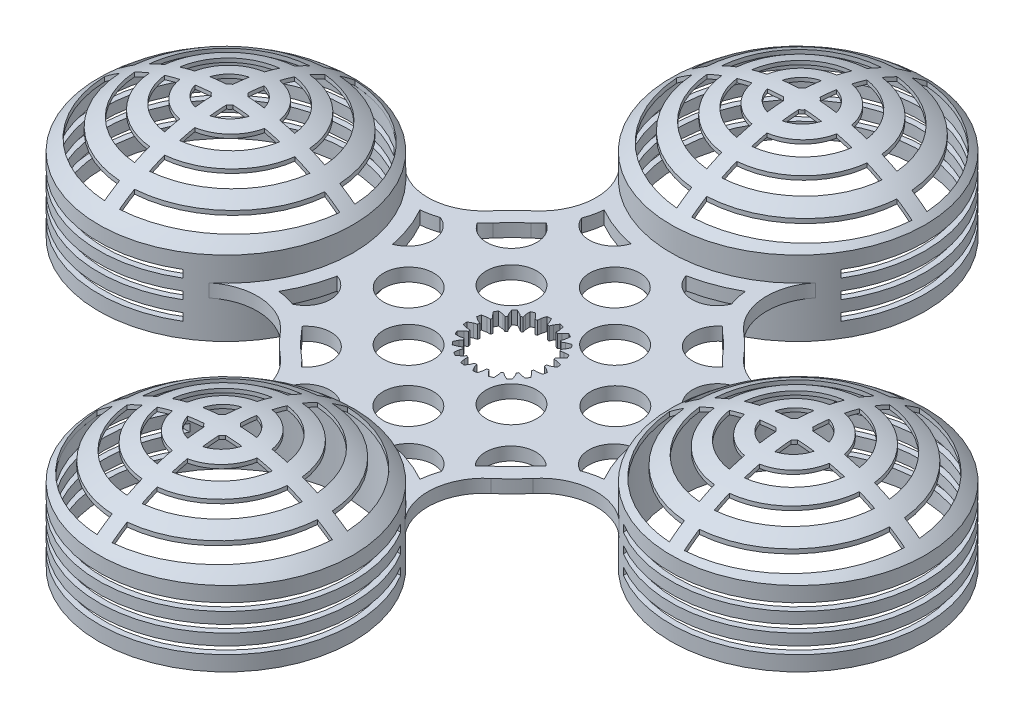
SolidWorks part; units mm, degrees
note: The reader was unsure of these and kept them because the rebuilt part matched: shared geometry of "Çizim1<3>".
ref_plane "Ön Düzlem" through (0, 0, 0) normal (0, 0, 1) x (1, 0, 0)
ref_plane "Üst Düzlem" through (0, 0, 0) normal (0, 1, 0) x (1, 0, 0)
ref_plane "Sağ Düzlem" through (0, 0, 0) normal (1, 0, 0) x (0, 0, -1)
sketch "Çizim1" plane through (0, 0, 0) normal (0, 1, 0) x (1, 0, 0)
  circle A0 centre (0, 0) radius 43.9658
  circle A1 centre (76.4658, 0) radius 32.5
  circle A2 centre (0, -76.4658) radius 32.5
  circle A3 centre (-76.4658, 0) radius 32.5
  circle A4 centre (0, 76.4658) radius 32.5
  point P14 (0, 0)
  dimension "D2" = 65
  dimension "D3" = 87.9316
  dimension "D1" = 4
extrude "Yükseklik-Ekstrüzyon1" add sketch "Çizim1" along normal blind 3.5 contours A0
extrude "Ekstrüzyon-İnce1" add sketch "Çizim1<3>" along normal mid plane 20 thin contours A3 | A2 | A1 | A4
sketch "Çizim1<3>" plane through (0, 0, 0) normal (0, 1, 0) x (1, 0, 0) same geometry as "Çizim1"
sketch "Çizim2" plane through (0, 3.5, 0) normal (0, 1, 0) x (1, 0, 0)
  line L0 (-2.9974, -9.6557) -> (-2.7583, -10.9582)
  line L1 (-1.7004, -11.1713) -> (-0.9756, -10.063)
  line L2 (-0.9756, -10.063) -> (-0.6518, -9.2771)
  line L3 (-0.1241, -9.2992) -> (0.1331, -10.1093)
  line L4 (0.1331, -10.1093) -> (0.7629, -11.2742)
  line L5 (1.835, -11.15) -> (2.1818, -9.872)
  line L6 (2.1818, -9.872) -> (2.2469, -9.0245)
  line L7 (2.7556, -8.8824) -> (3.2505, -9.5734)
  line L8 (3.2505, -9.5734) -> (4.2095, -10.4867)
  line L9 (5.1907, -10.0373) -> (5.1257, -8.7146)
  line L10 (5.1257, -8.7146) -> (4.9257, -7.8885)
  line L11 (5.3655, -7.5961) -> (6.0498, -8.1004)
  line L12 (6.0498, -8.1004) -> (7.244, -8.6726)
  line L13 (8.0383, -7.942) -> (7.5677, -6.7042)
  line L14 (7.5677, -6.7042) -> (7.1223, -5.9803)
  line L15 (7.4503, -5.5663) -> (8.2568, -5.8345)
  line L16 (8.2568, -5.8345) -> (9.5695, -6.0096)
  line L17 (10.0991, -5.0693) -> (9.269, -4.0375)
  line L18 (9.269, -4.0375) -> (8.6217, -3.4867)
  line L19 (8.8057, -2.9916) -> (9.6557, -2.9974)
  line L20 (9.6557, -2.9974) -> (10.9582, -2.7583)
  line L21 (11.1713, -1.7004) -> (10.063, -0.9756)
  line L22 (10.063, -0.9756) -> (9.2771, -0.6518)
  line L23 (9.2992, -0.1241) -> (10.1093, 0.1331)
  line L24 (10.1093, 0.1331) -> (11.2742, 0.7629)
  line L25 (11.15, 1.835) -> (9.872, 2.1818)
  line L26 (9.872, 2.1818) -> (9.0245, 2.2469)
  line L27 (8.8824, 2.7556) -> (9.5734, 3.2505)
  line L28 (9.5734, 3.2505) -> (10.4867, 4.2095)
  line L29 (10.0373, 5.1907) -> (8.7146, 5.1257)
  line L30 (8.7146, 5.1257) -> (7.8885, 4.9257)
  line L31 (7.5961, 5.3655) -> (8.1004, 6.0498)
  line L32 (8.1004, 6.0498) -> (8.6726, 7.244)
  line L33 (7.942, 8.0383) -> (6.7042, 7.5677)
  line L34 (6.7042, 7.5677) -> (5.9803, 7.1223)
  line L35 (5.5663, 7.4503) -> (5.8345, 8.2568)
  line L36 (5.8345, 8.2568) -> (6.0096, 9.5695)
  line L37 (5.0693, 10.0991) -> (4.0375, 9.269)
  line L38 (4.0375, 9.269) -> (3.4867, 8.6217)
  line L39 (2.9916, 8.8057) -> (2.9974, 9.6557)
  line L40 (2.9974, 9.6557) -> (2.7583, 10.9582)
  line L41 (1.7004, 11.1713) -> (0.9756, 10.063)
  line L42 (0.9756, 10.063) -> (0.6518, 9.2771)
  line L43 (0.1241, 9.2992) -> (-0.1331, 10.1093)
  line L44 (-0.1331, 10.1093) -> (-0.7629, 11.2742)
  line L45 (-1.835, 11.15) -> (-2.1818, 9.872)
  line L46 (-2.1818, 9.872) -> (-2.2469, 9.0245)
  line L47 (-2.7556, 8.8824) -> (-3.2505, 9.5734)
  line L48 (-3.2505, 9.5734) -> (-4.2095, 10.4867)
  line L49 (-5.1907, 10.0373) -> (-5.1257, 8.7146)
  line L50 (-5.1257, 8.7146) -> (-4.9257, 7.8885)
  line L51 (-5.3655, 7.5961) -> (-6.0498, 8.1004)
  line L52 (-6.0498, 8.1004) -> (-7.244, 8.6726)
  line L53 (-8.0383, 7.942) -> (-7.5677, 6.7042)
  line L54 (-7.5677, 6.7042) -> (-7.1223, 5.9803)
  line L55 (-7.4503, 5.5663) -> (-8.2568, 5.8345)
  line L56 (-8.2568, 5.8345) -> (-9.5695, 6.0096)
  line L57 (-10.0991, 5.0693) -> (-9.269, 4.0375)
  line L58 (-9.269, 4.0375) -> (-8.6217, 3.4867)
  line L59 (-8.8057, 2.9916) -> (-9.6557, 2.9974)
  line L60 (-9.6557, 2.9974) -> (-10.9582, 2.7583)
  line L61 (-11.1713, 1.7004) -> (-10.063, 0.9756)
  line L62 (-10.063, 0.9756) -> (-9.2771, 0.6518)
  line L63 (-9.2992, 0.1241) -> (-10.1093, -0.1331)
  line L64 (-10.1093, -0.1331) -> (-11.2742, -0.7629)
  line L65 (-11.15, -1.835) -> (-9.872, -2.1818)
  line L66 (-9.872, -2.1818) -> (-9.0245, -2.2469)
  line L67 (-8.8824, -2.7556) -> (-9.5734, -3.2505)
  line L68 (-9.5734, -3.2505) -> (-10.4867, -4.2095)
  line L69 (-10.0373, -5.1907) -> (-8.7146, -5.1257)
  line L70 (-8.7146, -5.1257) -> (-7.8885, -4.9257)
  line L71 (-7.5961, -5.3655) -> (-8.1004, -6.0498)
  line L72 (-8.1004, -6.0498) -> (-8.6726, -7.244)
  line L73 (-7.942, -8.0383) -> (-6.7042, -7.5677)
  line L74 (-6.7042, -7.5677) -> (-5.9803, -7.1223)
  line L75 (-5.5663, -7.4503) -> (-5.8345, -8.2568)
  line L76 (-5.8345, -8.2568) -> (-6.0096, -9.5695)
  line L77 (-5.0693, -10.0991) -> (-4.0375, -9.269)
  line L78 (-4.0375, -9.269) -> (-3.4867, -8.6217)
  line L79 (-2.9916, -8.8057) -> (-2.9974, -9.6557)
  line L160 (-2.6972, -9.6294) -> (-2.4984, -10.7125)
  line L161 (-1.8449, -10.8442) -> (-1.2422, -9.9226)
  line L162 (-1.2422, -9.9226) -> (-0.8457, -8.9602)
  line L163 (0.0956, -8.9995) -> (0.4104, -9.9916)
  line L164 (0.4104, -9.9916) -> (0.9342, -10.9603)
  line L165 (1.5965, -10.8835) -> (1.8849, -9.8208)
  line L166 (1.8849, -9.8208) -> (1.9646, -8.783)
  line L167 (2.8719, -8.5295) -> (3.4779, -9.3757)
  line L168 (3.4779, -9.3757) -> (4.2754, -10.1351)
  line L169 (4.8815, -9.8575) -> (4.8274, -8.7576)
  line L170 (4.8274, -8.7576) -> (4.5825, -7.746)
  line L171 (5.3671, -7.2246) -> (6.2049, -7.8421)
  line L172 (6.2049, -7.8421) -> (7.1981, -8.3179)
  line L173 (7.6887, -7.8666) -> (7.2974, -6.8373)
  line L174 (7.2974, -6.8373) -> (6.7519, -5.9508)
  line L175 (7.3369, -5.2125) -> (8.3246, -5.5409)
  line L176 (8.3246, -5.5409) -> (9.4162, -5.6865)
  line L177 (9.7433, -5.1056) -> (9.0531, -4.2476)
  line L178 (9.0531, -4.2476) -> (8.2603, -3.5731)
  line L179 (8.5886, -2.6901) -> (9.6294, -2.6972)
  line L180 (9.6294, -2.6972) -> (10.7125, -2.4984)
  line L181 (10.8442, -1.8449) -> (9.9226, -1.2422)
  line L182 (9.9226, -1.2422) -> (8.9602, -0.8457)
  line L183 (8.9995, 0.0956) -> (9.9916, 0.4104)
  line L184 (9.9916, 0.4104) -> (10.9603, 0.9342)
  line L185 (10.8835, 1.5965) -> (9.8208, 1.8849)
  line L186 (9.8208, 1.8849) -> (8.783, 1.9646)
  line L187 (8.5295, 2.8719) -> (9.3757, 3.4779)
  line L188 (9.3757, 3.4779) -> (10.1351, 4.2754)
  line L189 (9.8575, 4.8815) -> (8.7576, 4.8274)
  line L190 (8.7576, 4.8274) -> (7.746, 4.5825)
  line L191 (7.2246, 5.3671) -> (7.8421, 6.2049)
  line L192 (7.8421, 6.2049) -> (8.3179, 7.1981)
  line L193 (7.8666, 7.6887) -> (6.8373, 7.2974)
  line L194 (6.8373, 7.2974) -> (5.9508, 6.7519)
  line L195 (5.2125, 7.3369) -> (5.5409, 8.3246)
  line L196 (5.5409, 8.3246) -> (5.6865, 9.4162)
  line L197 (5.1056, 9.7433) -> (4.2476, 9.0531)
  line L198 (4.2476, 9.0531) -> (3.5731, 8.2603)
  line L199 (2.6901, 8.5886) -> (2.6972, 9.6294)
  line L200 (2.6972, 9.6294) -> (2.4984, 10.7125)
  line L201 (1.8449, 10.8442) -> (1.2422, 9.9226)
  line L202 (1.2422, 9.9226) -> (0.8457, 8.9602)
  line L203 (-0.0956, 8.9995) -> (-0.4104, 9.9916)
  line L204 (-0.4104, 9.9916) -> (-0.9342, 10.9603)
  line L205 (-1.5965, 10.8835) -> (-1.8849, 9.8208)
  line L206 (-1.8849, 9.8208) -> (-1.9646, 8.783)
  line L207 (-2.8719, 8.5295) -> (-3.4779, 9.3757)
  line L208 (-3.4779, 9.3757) -> (-4.2754, 10.1351)
  line L209 (-4.8815, 9.8575) -> (-4.8274, 8.7576)
  line L210 (-4.8274, 8.7576) -> (-4.5825, 7.746)
  line L211 (-5.3671, 7.2246) -> (-6.2049, 7.8421)
  line L212 (-6.2049, 7.8421) -> (-7.1981, 8.3179)
  line L213 (-7.6887, 7.8666) -> (-7.2974, 6.8373)
  line L214 (-7.2974, 6.8373) -> (-6.7519, 5.9508)
  line L215 (-7.3369, 5.2125) -> (-8.3246, 5.5409)
  line L216 (-8.3246, 5.5409) -> (-9.4162, 5.6865)
  line L217 (-9.7433, 5.1056) -> (-9.0531, 4.2476)
  line L218 (-9.0531, 4.2476) -> (-8.2603, 3.5731)
  line L219 (-8.5886, 2.6901) -> (-9.6294, 2.6972)
  line L220 (-9.6294, 2.6972) -> (-10.7125, 2.4984)
  line L221 (-10.8442, 1.8449) -> (-9.9226, 1.2422)
  line L222 (-9.9226, 1.2422) -> (-8.9602, 0.8457)
  line L223 (-8.9995, -0.0956) -> (-9.9916, -0.4104)
  line L224 (-9.9916, -0.4104) -> (-10.9603, -0.9342)
  line L225 (-10.8835, -1.5965) -> (-9.8208, -1.8849)
  line L226 (-9.8208, -1.8849) -> (-8.783, -1.9646)
  line L227 (-8.5295, -2.8719) -> (-9.3757, -3.4779)
  line L228 (-9.3757, -3.4779) -> (-10.1351, -4.2754)
  line L229 (-9.8575, -4.8815) -> (-8.7576, -4.8274)
  line L230 (-8.7576, -4.8274) -> (-7.746, -4.5825)
  line L231 (-7.2246, -5.3671) -> (-7.8421, -6.2049)
  line L232 (-7.8421, -6.2049) -> (-8.3179, -7.1981)
  line L233 (-7.8666, -7.6887) -> (-6.8373, -7.2974)
  line L234 (-6.8373, -7.2974) -> (-5.9508, -6.7519)
  line L235 (-5.2125, -7.3369) -> (-5.5409, -8.3246)
  line L236 (-5.5409, -8.3246) -> (-5.6865, -9.4162)
  line L237 (-5.1056, -9.7433) -> (-4.2476, -9.0531)
  line L238 (-4.2476, -9.0531) -> (-3.5731, -8.2603)
  line L239 (-2.6901, -8.5886) -> (-2.6972, -9.6294)
  arc A0 (-2.7583, -10.9582) -> (-1.7004, -11.1713) centre (0, 0) ccw
  arc A1 (-0.6518, -9.2771) -> (-0.1241, -9.2992) centre (0, 0) ccw
  arc A2 (0.7629, -11.2742) -> (1.835, -11.15) centre (0, 0) ccw
  arc A3 (2.2469, -9.0245) -> (2.7556, -8.8824) centre (0, 0) ccw
  arc A4 (4.2095, -10.4867) -> (5.1907, -10.0373) centre (0, 0) ccw
  arc A5 (4.9257, -7.8885) -> (5.3655, -7.5961) centre (0, 0) ccw
  arc A6 (7.244, -8.6726) -> (8.0383, -7.942) centre (0, 0) ccw
  arc A7 (7.1223, -5.9803) -> (7.4503, -5.5663) centre (0, 0) ccw
  arc A8 (9.5695, -6.0096) -> (10.0991, -5.0693) centre (0, 0) ccw
  arc A9 (8.6217, -3.4867) -> (8.8057, -2.9916) centre (0, 0) ccw
  arc A10 (10.9582, -2.7583) -> (11.1713, -1.7004) centre (0, 0) ccw
  arc A11 (9.2771, -0.6518) -> (9.2992, -0.1241) centre (0, 0) ccw
  arc A12 (11.2742, 0.7629) -> (11.15, 1.835) centre (0, 0) ccw
  arc A13 (9.0245, 2.2469) -> (8.8824, 2.7556) centre (0, 0) ccw
  arc A14 (10.4867, 4.2095) -> (10.0373, 5.1907) centre (0, 0) ccw
  arc A15 (7.8885, 4.9257) -> (7.5961, 5.3655) centre (0, 0) ccw
  arc A16 (8.6726, 7.244) -> (7.942, 8.0383) centre (0, 0) ccw
  arc A17 (5.9803, 7.1223) -> (5.5663, 7.4503) centre (0, 0) ccw
  arc A18 (6.0096, 9.5695) -> (5.0693, 10.0991) centre (0, 0) ccw
  arc A19 (3.4867, 8.6217) -> (2.9916, 8.8057) centre (0, 0) ccw
  arc A20 (2.7583, 10.9582) -> (1.7004, 11.1713) centre (0, 0) ccw
  arc A21 (0.6518, 9.2771) -> (0.1241, 9.2992) centre (0, 0) ccw
  arc A22 (-0.7629, 11.2742) -> (-1.835, 11.15) centre (0, 0) ccw
  arc A23 (-2.2469, 9.0245) -> (-2.7556, 8.8824) centre (0, 0) ccw
  arc A24 (-4.2095, 10.4867) -> (-5.1907, 10.0373) centre (0, 0) ccw
  arc A25 (-4.9257, 7.8885) -> (-5.3655, 7.5961) centre (0, 0) ccw
  arc A26 (-7.244, 8.6726) -> (-8.0383, 7.942) centre (0, 0) ccw
  arc A27 (-7.1223, 5.9803) -> (-7.4503, 5.5663) centre (0, 0) ccw
  arc A28 (-9.5695, 6.0096) -> (-10.0991, 5.0693) centre (0, 0) ccw
  arc A29 (-8.6217, 3.4867) -> (-8.8057, 2.9916) centre (0, 0) ccw
  arc A30 (-10.9582, 2.7583) -> (-11.1713, 1.7004) centre (0, 0) ccw
  arc A31 (-9.2771, 0.6518) -> (-9.2992, 0.1241) centre (0, 0) ccw
  arc A32 (-11.2742, -0.7629) -> (-11.15, -1.835) centre (0, 0) ccw
  arc A33 (-9.0245, -2.2469) -> (-8.8824, -2.7556) centre (0, 0) ccw
  arc A34 (-10.4867, -4.2095) -> (-10.0373, -5.1907) centre (0, 0) ccw
  arc A35 (-7.8885, -4.9257) -> (-7.5961, -5.3655) centre (0, 0) ccw
  arc A36 (-8.6726, -7.244) -> (-7.942, -8.0383) centre (0, 0) ccw
  arc A37 (-5.9803, -7.1223) -> (-5.5663, -7.4503) centre (0, 0) ccw
  arc A38 (-6.0096, -9.5695) -> (-5.0693, -10.0991) centre (0, 0) ccw
  arc A39 (-3.4867, -8.6217) -> (-2.9916, -8.8057) centre (0, 0) ccw
  arc A80 (-2.4984, -10.7125) -> (-1.8449, -10.8442) centre (0, 0) ccw
  arc A81 (-0.8457, -8.9602) -> (0.0956, -8.9995) centre (0, 0) ccw
  arc A82 (0.9342, -10.9603) -> (1.5965, -10.8835) centre (0, 0) ccw
  arc A83 (1.9646, -8.783) -> (2.8719, -8.5295) centre (0, 0) ccw
  arc A84 (4.2754, -10.1351) -> (4.8815, -9.8575) centre (0, 0) ccw
  arc A85 (4.5825, -7.746) -> (5.3671, -7.2246) centre (0, 0) ccw
  arc A86 (7.1981, -8.3179) -> (7.6887, -7.8666) centre (0, 0) ccw
  arc A87 (6.7519, -5.9508) -> (7.3369, -5.2125) centre (0, 0) ccw
  arc A88 (9.4162, -5.6865) -> (9.7433, -5.1056) centre (0, 0) ccw
  arc A89 (8.2603, -3.5731) -> (8.5886, -2.6901) centre (0, 0) ccw
  arc A90 (10.7125, -2.4984) -> (10.8442, -1.8449) centre (0, 0) ccw
  arc A91 (8.9602, -0.8457) -> (8.9995, 0.0956) centre (0, 0) ccw
  arc A92 (10.9603, 0.9342) -> (10.8835, 1.5965) centre (0, 0) ccw
  arc A93 (8.783, 1.9646) -> (8.5295, 2.8719) centre (0, 0) ccw
  arc A94 (10.1351, 4.2754) -> (9.8575, 4.8815) centre (0, 0) ccw
  arc A95 (7.746, 4.5825) -> (7.2246, 5.3671) centre (0, 0) ccw
  arc A96 (8.3179, 7.1981) -> (7.8666, 7.6887) centre (0, 0) ccw
  arc A97 (5.9508, 6.7519) -> (5.2125, 7.3369) centre (0, 0) ccw
  arc A98 (5.6865, 9.4162) -> (5.1056, 9.7433) centre (0, 0) ccw
  arc A99 (3.5731, 8.2603) -> (2.6901, 8.5886) centre (0, 0) ccw
  arc A100 (2.4984, 10.7125) -> (1.8449, 10.8442) centre (0, 0) ccw
  arc A101 (0.8457, 8.9602) -> (-0.0956, 8.9995) centre (0, 0) ccw
  arc A102 (-0.9342, 10.9603) -> (-1.5965, 10.8835) centre (0, 0) ccw
  arc A103 (-1.9646, 8.783) -> (-2.8719, 8.5295) centre (0, 0) ccw
  arc A104 (-4.2754, 10.1351) -> (-4.8815, 9.8575) centre (0, 0) ccw
  arc A105 (-4.5825, 7.746) -> (-5.3671, 7.2246) centre (0, 0) ccw
  arc A106 (-7.1981, 8.3179) -> (-7.6887, 7.8666) centre (0, 0) ccw
  arc A107 (-6.7519, 5.9508) -> (-7.3369, 5.2125) centre (0, 0) ccw
  arc A108 (-9.4162, 5.6865) -> (-9.7433, 5.1056) centre (0, 0) ccw
  arc A109 (-8.2603, 3.5731) -> (-8.5886, 2.6901) centre (0, 0) ccw
  arc A110 (-10.7125, 2.4984) -> (-10.8442, 1.8449) centre (0, 0) ccw
  arc A111 (-8.9602, 0.8457) -> (-8.9995, -0.0956) centre (0, 0) ccw
  arc A112 (-10.9603, -0.9342) -> (-10.8835, -1.5965) centre (0, 0) ccw
  arc A113 (-8.783, -1.9646) -> (-8.5295, -2.8719) centre (0, 0) ccw
  arc A114 (-10.1351, -4.2754) -> (-9.8575, -4.8815) centre (0, 0) ccw
  arc A115 (-7.746, -4.5825) -> (-7.2246, -5.3671) centre (0, 0) ccw
  arc A116 (-8.3179, -7.1981) -> (-7.8666, -7.6887) centre (0, 0) ccw
  arc A117 (-5.9508, -6.7519) -> (-5.2125, -7.3369) centre (0, 0) ccw
  arc A118 (-5.6865, -9.4162) -> (-5.1056, -9.7433) centre (0, 0) ccw
  arc A119 (-3.5731, -8.2603) -> (-2.6901, -8.5886) centre (0, 0) ccw
  dimension "D2" = 0.3
extrude "Kes-Ekstrüzyon1" cut sketch "Çizim2" against normal through all contours L238 A119 L239 L160 A80 L161 L162 A81 L163 L164 A82 L165 L166 A83 L167 L168 A84 L169 L170 A85 L171 L172 A86 L173 L174 A87 L175 L176 A88 L177 L178 A89 L179 L180 A90 L181 L182 A91 L183 L184 A92 L185 L186 A93 L187 L188 A94 L189 L190 A95 L191 | L78 A39 L79 L0 A0 L1 L2 A1 L3 L4 A2 L5 L6 A3 L7 L8 A4 L9 L10 A5 L11 L12 A6 L13 L14 A7 L15 L16 A8 L17 L18 A9 L19 L20 A10 L21 L22 A11 L23 L24 A12 L25 L26 A13 L27 L28 A14 L29 L30 A15 L31
sketch "Çizim3" plane through (0, 3.5, 0) normal (0, 1, 0) x (1, 0, 0)
  line L0 (107.611, -9.2857) -> (45.3206, 9.2857)
  circle A1 centre (76.4658, 0) radius 32.5
  circle A3 centre (76.4658, 0) radius 32.5 construction
  point P11 (76.4658, 0)
ref_plane "Düzlem1" through (6.2421, 0, -20.9367) normal (0.2857, 0, -0.9583) x (-0.9583, 0, -0.2857)
sketch "Çizim4" plane through (6.2421, 0, -20.9367) normal (0.2857, 0, -0.9583) x (-0.9583, 0, -0.2857)
  line L0 (-39.2783, 10) -> (-107.2783, 10) construction
  line L1 (-40.7783, 10) -> (-105.7783, 10) construction
  line L3 (-73.2783, 30.9693) -> (-73.2783, 0)
  line L4 (-39.2783, -10) -> (-39.2783, 10) construction
  line L5 (-40.7783, 10) -> (-105.7783, 10)
  line L6 (-105.7783, 10) -> (-107.2783, 10)
  line L7 (-40.7783, 10) -> (-39.2783, 10)
  arc A3 (-107.2783, 10) -> (-39.2783, 10) centre (-73.2783, -28.9287) cw
  arc A4 (-105.7783, 10) -> (-40.7783, 10) centre (-73.2783, -28.9287) cw
  arc A5 (-106.6402, 9.2639) -> (-39.9191, 9.2663) centre (-73.2783, -28.9287) cw construction
  arc A6 (-107.2811, 9.9976) -> (-39.2783, 10) centre (-73.2783, -28.9287) cw construction
revolve "Döndür5" add sketch "Çizim4" angle 360 about L3
pattern_circular "Dairesel Kaplama1" count 4 over 360 about axis through (0, 0, 0) along (0, 1, 0) of "Döndür5"
fillet "Radyus1" radius 15 8 edges at (-7.5451, 1.75, 43.3135) (7.5451, 1.75, 43.3135) (-43.3135, 1.75, -7.5451) (-43.3135, 1.75, 7.5451) (43.3135, 1.75, 7.5451) (43.3135, 1.75, -7.5451) (7.5451, 1.75, -43.3135) (-7.5451, 1.75, -43.3135)
sketch "Çizim6" plane through (0, 3.5, 0) normal (0, 1, 0) x (1, 0, 0)
  line L1 (-52.2515, 78.4593) -> (48.6953, 78.4593)
  line L2 (-52.2515, 78.4593) -> (-52.2515, 74.4593)
  line L3 (-52.2515, 74.4593) -> (48.6953, 74.4593)
  line L4 (48.6953, 78.4593) -> (48.6953, 74.4593)
  line L5 (-1.0076, 123.3421) -> (2.9924, 123.3421)
  line L6 (-1.0076, 123.3421) -> (-1.0076, 29.9642)
  line L7 (-1.0076, 29.9642) -> (2.9924, 29.9642)
  line L8 (2.9924, 123.3421) -> (2.9924, 29.9642)
  circle A0 centre (0.9924, 76.4593) radius 31.5
  circle A1 centre (0.9924, 76.4593) radius 27.5
  circle A3 centre (0, 76.4658) radius 34
  circle A6 centre (0.9924, 76.4593) radius 23.5
  circle A7 centre (0.9924, 76.4593) radius 19.5
  circle A8 centre (0.9924, 76.4593) radius 15.5
  circle A9 centre (0.9924, 76.4593) radius 11.5
  circle A10 centre (0.9924, 76.4593) radius 7.5
  circle A11 centre (0.9924, 76.4593) radius 3.5
  circle A14 centre (0, 76.4658) radius 34
  dimension "D10" = 4
  dimension "D11" = 4
  dimension "D1" = 0
  dimension "D3" = 4
  dimension "D4" = 4
  dimension "D5" = 4
  dimension "D6" = 4
  dimension "D7" = 4
  dimension "D8" = 4
  dimension "D9" = 4
extrude "Kes-Ekstrüzyon4" cut sketch "Çizim6" along normal through all contours A1 L1 A0 L8 | A7 L1 A6 L8 | A9 L1 A8 L8 | A11 L1 A10 L8 | A11 L8 A10 L3 | A11 L3 A10 L6 | A11 L6 A10 L1 | A9 L6 A8 L1 | A7 L6 A6 L1 | A1 L6 A0 L1 | A1 L3 A0 L6 | A7 L3 A6 L6 | A9 L3 A8 L6 | A9 L8 A8 L3 | A7 L8 A6 L3 | A1 L8 A0 L3
pattern_circular "Dairesel Kaplama2" count 4 over 360 about axis through (0, 0, 0) along (0, 1, 0) of "Kes-Ekstrüzyon4"
sketch "Çizim7" plane through (0, 3.5, 0) normal (0, 1, 0) x (1, 0, 0)
  line L0 (35.4078, 201.0327) -> (338.7411, 201.0327) construction
  circle A33 centre (-13.8045, 13.6521) radius 6.7064
  circle A36 centre (0.5146, 26.9404) radius 6.7064
  circle A38 centre (13.8253, 13.726) radius 6.7064
  arc A76 (43.4818, 18.8695) -> (43.4818, -18.8695) centre (76.4658, 0) ccw
  arc A77 (43.4818, -18.8695) -> (30.682, -25.6101) centre (45.2685, -37.7853) ccw
  arc A78 (25.6101, -30.682) -> (30.682, -25.6101) centre (0, 0) ccw
  arc A79 (25.6101, -30.682) -> (18.8695, -43.4818) centre (37.7853, -45.2685) ccw
  arc A80 (18.8695, -43.4818) -> (-18.8695, -43.4818) centre (0, -76.4658) ccw
  arc A81 (-18.8695, -43.4818) -> (-25.6101, -30.682) centre (-37.7853, -45.2685) ccw
  arc A82 (-30.682, -25.6101) -> (-25.6101, -30.682) centre (0, 0) ccw
  arc A83 (-30.682, -25.6101) -> (-43.4818, -18.8695) centre (-45.2685, -37.7853) ccw
  arc A84 (-43.4818, -18.8695) -> (-43.4818, 18.8695) centre (-76.4658, 0) ccw
  arc A85 (-43.4818, 18.8695) -> (-30.682, 25.6101) centre (-45.2685, 37.7853) ccw
  arc A86 (-25.6101, 30.682) -> (-30.682, 25.6101) centre (0, 0) ccw
  arc A87 (-25.6101, 30.682) -> (-18.8695, 43.4818) centre (-37.7853, 45.2685) ccw
  arc A88 (-18.8695, 43.4818) -> (18.8695, 43.4818) centre (0, 76.4658) ccw
  arc A89 (18.8695, 43.4818) -> (25.6101, 30.682) centre (37.7853, 45.2685) ccw
  arc A90 (30.682, 25.6101) -> (25.6101, 30.682) centre (0, 0) ccw
  circle A91 centre (28.0636, -0.4544) radius 6.7064
  circle A92 centre (13.7414, -13.9006) radius 6.7064
  circle A93 centre (-13.7682, -13.8827) radius 6.7064
  circle A94 centre (-27.0243, -0.5966) radius 6.7064
  circle A95 centre (-27.0722, -28.0232) radius 6.7064
  circle A96 centre (0.3544, -28.0711) radius 6.7064
  circle A97 centre (28.0286, -28.3768) radius 6.7064
  circle A98 centre (41.3351, -14.11) radius 6.7064
  circle A99 centre (41.2643, 13.6982) radius 6.7064
  circle A100 centre (27.9571, 27.0371) radius 6.7064
  circle A101 centre (-41.4371, 13.5766) radius 6.7064
  circle A102 centre (-41.4071, -13.8386) radius 6.7064
  circle A103 centre (-27.0529, 26.9639) radius 6.7064
  circle A104 centre (13.696, 41.1895) radius 6.7064
  circle A105 centre (-13.8526, 41.2127) radius 6.7064
  circle A106 centre (-13.8137, -41.5622) radius 6.7064
  circle A107 centre (13.8018, -41.4663) radius 6.7064
  arc A108 (30.682, 25.6101) -> (43.4818, 18.8695) centre (45.2685, 37.7853) ccw
  arc A109 (54.8187, 26.2184) -> (54.8187, -26.2184) centre (76.4658, 0) ccw
  arc A110 (33.7529, 28.1733) -> (54.8187, 26.2184) centre (45.2685, 37.7853) ccw
  arc A111 (33.7529, 28.1733) -> (28.1733, 33.7529) centre (0, 0) ccw
  arc A112 (26.2184, 54.8187) -> (28.1733, 33.7529) centre (37.7853, 45.2685) ccw
  arc A113 (-26.2184, 54.8187) -> (26.2184, 54.8187) centre (0, 76.4658) ccw
  arc A114 (-28.1733, 33.7529) -> (-26.2184, 54.8187) centre (-37.7853, 45.2685) ccw
  arc A115 (-28.1733, 33.7529) -> (-33.7529, 28.1733) centre (0, 0) ccw
  arc A116 (-54.8187, 26.2184) -> (-33.7529, 28.1733) centre (-45.2685, 37.7853) ccw
  arc A117 (-54.8187, -26.2184) -> (-54.8187, 26.2184) centre (-76.4658, 0) ccw
  arc A118 (-33.7529, -28.1733) -> (-54.8187, -26.2184) centre (-45.2685, -37.7853) ccw
  arc A119 (-33.7529, -28.1733) -> (-28.1733, -33.7529) centre (0, 0) ccw
  arc A120 (-26.2184, -54.8187) -> (-28.1733, -33.7529) centre (-37.7853, -45.2685) ccw
  arc A121 (26.2184, -54.8187) -> (-26.2184, -54.8187) centre (0, -76.4658) ccw
  arc A122 (28.1733, -33.7529) -> (26.2184, -54.8187) centre (37.7853, -45.2685) ccw
  arc A123 (28.1733, -33.7529) -> (33.7529, -28.1733) centre (0, 0) ccw
  arc A124 (54.8187, -26.2184) -> (33.7529, -28.1733) centre (45.2685, -37.7853) ccw
  arc A125 (54.8187, 26.2184) -> (54.8187, -26.2184) centre (76.4658, 0) ccw
  arc A126 (33.7529, 28.1733) -> (54.8187, 26.2184) centre (45.2685, 37.7853) ccw
  arc A127 (33.7529, 28.1733) -> (28.1733, 33.7529) centre (0, 0) ccw
  arc A128 (26.2184, 54.8187) -> (28.1733, 33.7529) centre (37.7853, 45.2685) ccw
  arc A129 (-26.2184, 54.8187) -> (26.2184, 54.8187) centre (0, 76.4658) ccw
  arc A130 (-28.1733, 33.7529) -> (-26.2184, 54.8187) centre (-37.7853, 45.2685) ccw
  arc A131 (-28.1733, 33.7529) -> (-33.7529, 28.1733) centre (0, 0) ccw
  arc A132 (-54.8187, 26.2184) -> (-33.7529, 28.1733) centre (-45.2685, 37.7853) ccw
  arc A133 (-54.8187, -26.2184) -> (-54.8187, 26.2184) centre (-76.4658, 0) ccw
  arc A134 (-33.7529, -28.1733) -> (-54.8187, -26.2184) centre (-45.2685, -37.7853) ccw
  arc A135 (-33.7529, -28.1733) -> (-28.1733, -33.7529) centre (0, 0) ccw
  arc A136 (-26.2184, -54.8187) -> (-28.1733, -33.7529) centre (-37.7853, -45.2685) ccw
  arc A137 (26.2184, -54.8187) -> (-26.2184, -54.8187) centre (0, -76.4658) ccw
  arc A138 (28.1733, -33.7529) -> (26.2184, -54.8187) centre (37.7853, -45.2685) ccw
  arc A139 (28.1733, -33.7529) -> (33.7529, -28.1733) centre (0, 0) ccw
  arc A140 (54.8187, -26.2184) -> (33.7529, -28.1733) centre (45.2685, -37.7853) ccw
  dimension "D1" = 0
  dimension "D2" = 4
extrude "Kes-Ekstrüzyon5" cut sketch "Çizim7" against normal through all contours A94 | A33 | A36 | A38 | A91 | A76 A98 A77 | A92 | A77 A97 A79 A78 | A79 A107 A80 | A96 | A93 | A81 A95 A83 A82 | A80 A106 A81 | A83 A102 A84 | A84 A101 A85 | A85 A103 A87 A86 | A87 A105 A88 | A88 A104 A89 | A108 A90 A89 A100 | A108 A99 A76
sketch "Çizim8" plane through (0, 0, 0) normal (0, 0, 1) x (1, 0, 0)
  line L1 (58.8187, 6) -> (114.6419, 6)
  line L2 (58.8187, 6) -> (58.8187, 4)
  line L3 (58.8187, 4) -> (114.6419, 4)
  line L4 (114.6419, 6) -> (114.6419, 4)
  line L9 (58.8187, -4) -> (114.6419, -4)
  line L10 (58.8187, -4) -> (58.8187, -6)
  line L11 (58.8187, -6) -> (114.6419, -6)
  line L12 (114.6419, -4) -> (114.6419, -6)
  line L13 (42.4658, -10) -> (110.4658, -10) construction
  line L14 (110.4658, -10) -> (110.4658, 10) construction
  line L15 (110.4658, -10) -> (110.4658, 10)
  line L16 (58.8187, 1) -> (58.8187, 4)
  line L17 (58.8187, 1) -> (114.6419, 1)
  line L18 (58.8187, 1) -> (58.8187, -1)
  line L19 (58.8187, -1) -> (114.6419, -1)
  line L20 (114.6419, 1) -> (114.6419, -1)
  line L21 (58.8187, -4) -> (58.8187, -1)
  line L22 (54.8187, 3.5) -> (54.8187, 0) construction
  line L24 (110.4658, 10) -> (42.4658, 10) construction
  dimension "D2" = 2
  dimension "D5" = 4
  dimension "D6" = 2
  dimension "D3" = 20
  dimension "D4" = 2
  dimension "D7" = 4
  dimension "D1" = 4
extrude "Kes-Ekstrüzyon6" cut sketch "Çizim8" against normal through all both and the other way through all contours L3 L15 L1 L2 | L18 L19 L15 L17 | L11 L15 L9 L10
pattern_circular "Dairesel Kaplama3" count 4 over 360 about axis through (0, 0, 0) along (0, 1, 0) of "Kes-Ekstrüzyon6"
equation "\"D5@Çizim8\"=\"D3@Çizim8\"/5"
equation "\"D2@Çizim8\"=\"D3@Çizim8\"/10"
equation "\"D6@Çizim8\"=\"D2@Çizim8\""
equation "\"D4@Çizim8\"=\"D2@Çizim8\""
